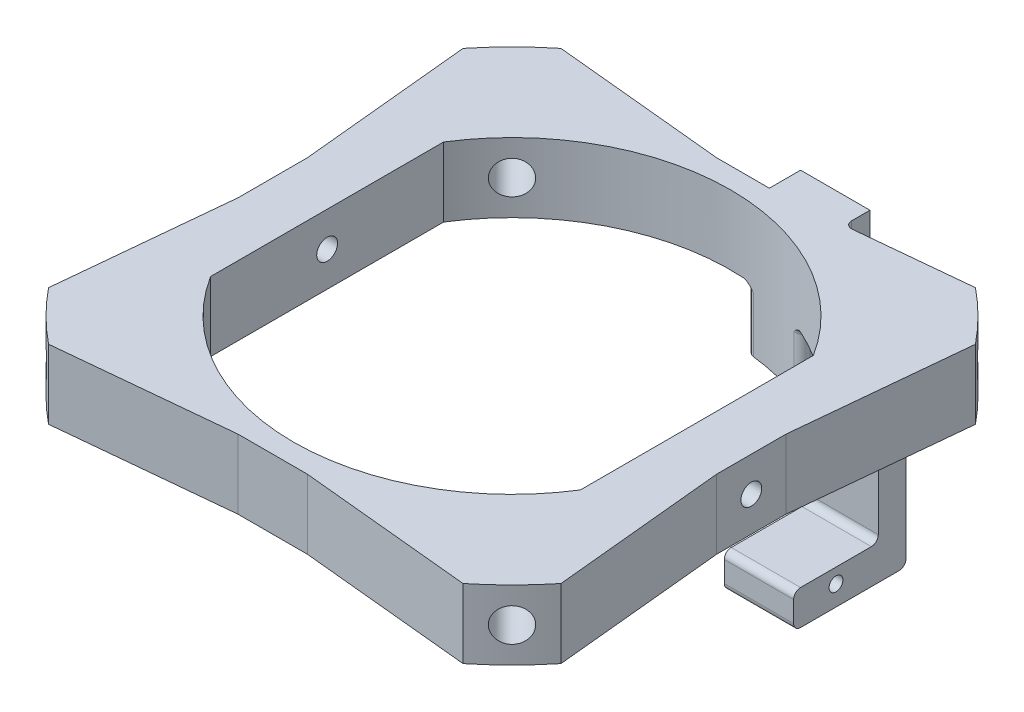
SolidWorks part; units mm, degrees
material "ABS"
ref_plane "Front Plane" through (0, 0, 0) normal (0, 0, 1) x (1, 0, 0)
ref_plane "Top Plane" through (0, 0, 0) normal (0, 1, 0) x (1, 0, 0)
ref_plane "Right Plane" through (0, 0, 0) normal (1, 0, 0) x (0, 0, -1)
sketch "Sketch1" plane through (0, 0, 0) normal (0, 1, 0) x (1, 0, 0)
  line L0 (0, 0) -> (0, -50000) construction
  line L1 (0, 0) -> (50000, 0) construction
  line L4 (-23.0054, -11) -> (-25.9, -11) construction
  line L5 (-25.9, -11) -> (-25.9, 11) construction
  line L6 (-23.0054, 11) -> (-25.9, 11) construction
  line L7 (-25.5, 0) -> (-25.5, -50000) construction
  line L10 (23.0054, 11) -> (25.9, 11) construction
  line L11 (25.9, -11) -> (25.9, 11) construction
  line L13 (23.0054, -11) -> (25.9, -11) construction
  line L14 (0, 0) -> (-33.5876, -33.5876) construction
  line L15 (0, 0) -> (-29.8709, -36.9321) construction
  line L16 (0, 0) -> (-36.9321, -29.8709) construction
  line L17 (-36.9321, -29.8709) -> (-34.5, -5)
  line L18 (-34.5, -5) -> (-34.5, 5)
  line L19 (-31.5, 0) -> (-31.5, -50000) construction
  line L20 (-29.8709, -36.9321) -> (-5, -34.5)
  line L21 (-5, -34.5) -> (5, -34.5)
  line L22 (-5, 34.5) -> (5, 34.5)
  line L23 (-29.8709, 36.9321) -> (-5, 34.5)
  line L24 (-36.9321, 29.8709) -> (-34.5, 5)
  line L27 (29.8709, 36.9321) -> (5, 34.5)
  line L28 (36.9321, 29.8709) -> (34.5, 5)
  line L29 (34.5, -5) -> (34.5, 5)
  line L30 (36.9321, -29.8709) -> (34.5, -5)
  line L31 (29.8709, -36.9321) -> (5, -34.5)
  line L33 (26.65, 16.7937) -> (26.65, -16.7937)
  line L35 (-26.65, 16.7937) -> (-26.65, -16.7937)
  circle A6 centre (0, 0) radius 15.5 construction
  circle A7 centre (0, 0) radius 21.5 construction
  circle A8 centre (0, 0) radius 25.5 construction
  arc A9 (26.65, 16.7937) -> (-26.65, 16.7937) centre (0, 0) ccw
  arc A11 (-36.9321, -29.8709) -> (-29.8709, -36.9321) centre (0, 0) ccw
  arc A12 (-36.9321, 29.8709) -> (-29.8709, 36.9321) centre (0, 0) cw
  arc A13 (36.9321, 29.8709) -> (29.8709, 36.9321) centre (0, 0) ccw
  arc A14 (36.9321, -29.8709) -> (29.8709, -36.9321) centre (0, 0) cw
  arc A15 (-26.65, -16.7937) -> (26.65, -16.7937) centre (0, 0) ccw
  point P13 (-25.9, 0)
  point P16 (-25.5, 0)
  point P35 (-34.5, 0)
  point P36 (0, 34.5)
  point P43 (0, -34.5)
  point P51 (0, 0)
  dimension "D1" = 31
  dimension "D7" = 95
  dimension "D2" = 6
  dimension "D3" = 4
  dimension "D4" = 0.4
  dimension "D5" = 22
  dimension "D8" = 45
  dimension "D9" = 5
  dimension "D10" = 5
  dimension "D11" = 5
  dimension "D12" = 3
  dimension "D13" = 0.75
  dimension "D6" = 6
extrude "Outer-Ring-body" add sketch "Sketch1" along normal blind 10
ref_plane "Plane1" through (0, 0, 0) normal (0.7071, 0, 0.7071) x (0.7071, 0, -0.7071)
ref_plane "TangentPlane1" through (33.5876, 0, -33.5876) normal (0.7071, 0, -0.7071) x (-0.7071, 0, -0.7071)
sketch "Sketch3" plane through (33.5876, 0, -33.5876) normal (0.7071, 0, -0.7071) x (-0.7071, 0, -0.7071)
  line L0 (-4.9931, 0) -> (4.9931, 0) construction
  line L1 (4.9931, 0) -> (4.9931, 10) construction
  line L2 (4.9931, 10) -> (-4.9931, 10) construction
  line L3 (-4.9931, 10) -> (-4.9931, 0) construction
  line L4 (0, 0) -> (0, 10) construction
  line L5 (-4.9931, 5) -> (4.9931, 5) construction
  circle A0 centre (0, 5) radius 2.413
  dimension "D1" = 4.826
extrude "Exterior-Mount-Holes" cut sketch "Sketch3" against normal up to surface (78.9074 mm away) up to face at (0, 5, -24.1468)
pattern_circular "CirPattern1" count 4 over 360 about axis through (0, 0, 0) along (0, 1, 0) of "Exterior-Mount-Holes"
ref_plane "MidPlane" through (7.6, 0, 0) normal (1, 0, 0) x (0, 0, -1)
sketch "Sketch4" plane through (7.6, 0, 0) normal (1, 0, 0) x (0, 0, -1)
  line L0 (0, 0) -> (0, -50000) construction
  line L1 (28, 0) -> (28, -50000) construction
  line L3 (29.8709, 0) -> (36.9321, 0) construction
  line L4 (28, 0) -> (28, -9)
  line L5 (28, -9) -> (40.2, -9)
  line L6 (40.2, -9) -> (40.2, -32.1)
  line L7 (40.2, -32.1) -> (28, -32.1)
  line L8 (28, -32.1) -> (28, -37.1)
  line L9 (28, -37.1) -> (44.2, -37.1)
  line L10 (44.2, -37.1) -> (44.2, -4)
  line L11 (44.2, -4) -> (39, -4)
  line L12 (39, -4) -> (39, 0)
  line L13 (28, 0) -> (28, 10)
  line L14 (5, 10) -> (29.8709, 10) construction
  line L17 (39, 0) -> (39, 10)
  line L18 (39, 10) -> (28, 10)
  line L19 (5, 0) -> (29.8709, 0) construction
  line L20 (34.1, -32.1) -> (34.1, -50032.1) construction
  line L21 (44, -20.55) -> (50044, -20.55) construction
  circle A0 centre (34.1, -34.2) radius 1
  circle A1 centre (34.1, -6.9) radius 1
  point P26 (34.1, -32.1)
  point P29 (40.2, -20.55)
  dimension "D10" = 2
  dimension "D1" = 28
  dimension "D2" = 23.1
  dimension "D3" = 5
  dimension "D4" = 5
  dimension "D5" = 9
  dimension "D6" = 4
  dimension "D7" = 12.2
  dimension "D8" = 12.2
  dimension "D9" = 11
  dimension "D11" = 2.1
  dimension "D12" = 44.2
extrude "Servo-Mount" add sketch "Sketch4" along normal mid plane 10
sketch "Sketch5" plane through (0, 0, 0) normal (0, -1, 0) x (1, 0, 0)
  line L0 (-26.65, -16.7937) -> (-26.65, 16.7937) construction
  line L1 (26.65, 16.7937) -> (26.65, -16.7937) construction
  line L2 (-26.65, -16.7937) -> (-26.65, 16.7937)
  line L3 (26.65, 16.7937) -> (26.65, -16.7937)
  arc A1 (26.65, 16.7937) -> (-26.65, 16.7937) centre (0, 0) ccw
  arc A2 (-26.65, -16.7937) -> (26.65, -16.7937) centre (0, 0) ccw
extrude "Cut-Extrude2" cut sketch "Sketch5" against normal mid plane 30
fillet "Fillet1" radius 1 10 edges at (7.6, -4, -39) (7.6, -4, -44.2) (7.6, -37.1, -44.2) (7.6, -32.1, -28) (7.6, -37.1, -28) (7.6, -32.1, -40.2) (7.6, -9, -40.2) (2.6, -4.5, -31.3925) (12.6, -4.5, -28.8702) (12.6, 5, -35.2432)
sketch "Sketch6" plane through (7.6, 0, 0) normal (1, 0, 0) x (0, 0, -1)
  line L0 (0, 0) -> (0, 50000) construction
  line L1 (-5, 5) -> (49995, 5) construction
  line L2 (-5, 10) -> (-5, 0) construction
  circle A0 centre (0, 5) radius 1.5
  point P7 (-5, 5)
  dimension "D1" = 3
extrude "Cut-Extrude3" cut sketch "Sketch6" against normal mid plane 100
fillet "Fillet2" radius 1 4 edges at (2.8548, 0, -31.6332) (12.167, 0, -29.5357) (2.6, 0, -33.4) (12.6, 0, -33.3526)
equation "\"D10@Sketch1\"=\"D9@Sketch1\""
